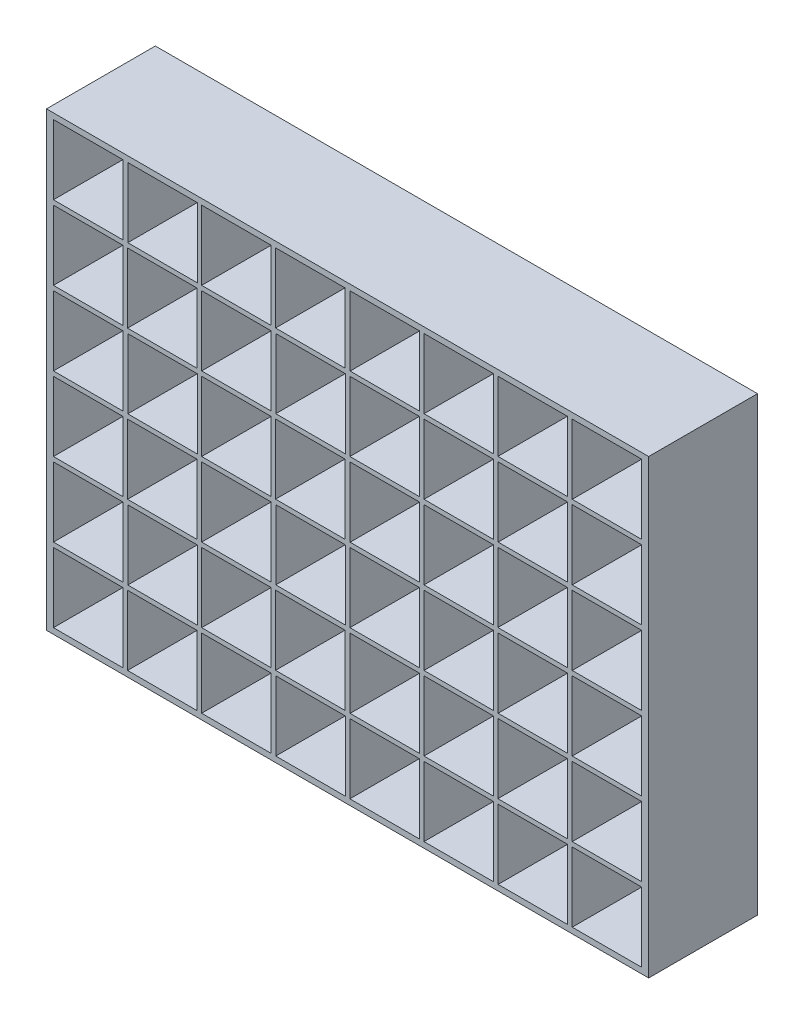
SolidWorks part; units mm, degrees
ref_plane "Front Plane" through (0, 0, 0) normal (0, 0, 1) x (1, 0, 0)
ref_plane "Top Plane" through (0, 0, 0) normal (0, 1, 0) x (1, 0, 0)
ref_plane "Right Plane" through (0, 0, 0) normal (1, 0, 0) x (0, 0, -1)
sketch "Sketch2" plane through (0, 0, 0) normal (0, 0, 1) x (1, 0, 0)
  line L0 (279.5621, 0) -> (0, 0) construction
  line L1 (0, 0) -> (-270, 0) construction
  line L2 (0, 213.5254) -> (0, 0) construction
  line L3 (0, 0) -> (0, -206.351) construction
  line L4 (279.5621, -160) -> (-260.4379, -160) construction
  line L5 (269.6997, 32) -> (-270, 32) construction
  line L6 (-270.3003, 96) -> (269.6997, 96) construction
  line L7 (254, 62) -> (194, 62)
  line L8 (269.6997, 160) -> (-270.3003, 155.1143) construction
  line L10 (-260, 195) -> (260, 195)
  line L11 (32, 207.3747) -> (32, -206.351) construction
  line L12 (-260.4379, -32) -> (279.5621, -32) construction
  line L13 (2.1959, 2) -> (62.1959, 2)
  line L14 (96, -206.351) -> (96, 207.3747) construction
  line L15 (2.1959, 2) -> (2.1959, 62)
  line L16 (160, 207.3747) -> (160, -206.351) construction
  line L17 (2.1959, 62) -> (62.1959, 62)
  line L18 (-260.4379, -96) -> (279.5621, -96) construction
  line L19 (224, -206.351) -> (224, 207.3747) construction
  line L20 (-32, 213.5254) -> (-32, -206.351) construction
  line L21 (62.1959, 2) -> (62.1959, 62)
  line L22 (-96, -206.351) -> (-96, 217.0649) construction
  line L23 (-260, 195) -> (-260, -195)
  line L24 (-160, 213.5254) -> (-160, -206.351) construction
  line L25 (-260, -195) -> (260, -195)
  line L26 (-224, -206.351) -> (-224, 207.3747) construction
  line L27 (66, 2) -> (126, 2)
  line L28 (66, 2) -> (66, 62)
  line L29 (66, 62) -> (126, 62)
  line L30 (126, 2) -> (126, 62)
  line L31 (260, 195) -> (260, -195)
  line L32 (-260, 195) -> (260, -195) construction
  line L33 (194, 2) -> (194, 62)
  line L34 (254, 2) -> (194, 2)
  line L35 (254, 2) -> (254, 62)
  line L36 (189.8041, 62) -> (129.8041, 62)
  line L37 (129.8041, 2) -> (129.8041, 62)
  line L38 (189.8041, 2) -> (129.8041, 2)
  line L39 (189.8041, 2) -> (189.8041, 62)
  line L40 (-2.1959, 62) -> (-62.1959, 62)
  line L41 (-62.1959, 2) -> (-62.1959, 62)
  line L42 (-2.1959, 2) -> (-62.1959, 2)
  line L43 (-2.1959, 2) -> (-2.1959, 62)
  line L44 (-189.8041, 2) -> (-189.8041, 62)
  line L45 (-189.8041, 2) -> (-129.8041, 2)
  line L46 (-129.8041, 2) -> (-129.8041, 62)
  line L47 (-189.8041, 62) -> (-129.8041, 62)
  line L48 (-66, 62) -> (-126, 62)
  line L49 (-126, 2) -> (-126, 62)
  line L50 (-66, 2) -> (-126, 2)
  line L51 (-66, 2) -> (-66, 62)
  line L52 (-254, 2) -> (-254, 62)
  line L53 (-254, 2) -> (-194, 2)
  line L54 (-194, 2) -> (-194, 62)
  line L55 (-254, 62) -> (-194, 62)
  line L56 (-254, 190) -> (-194, 190)
  line L57 (-194, 190) -> (-194, 130)
  line L58 (-254, 130) -> (-194, 130)
  line L59 (-254, 190) -> (-254, 130)
  line L60 (-189.8041, 190) -> (-129.8041, 190)
  line L61 (-129.8041, 190) -> (-129.8041, 130)
  line L62 (-189.8041, 130) -> (-129.8041, 130)
  line L63 (-189.8041, 190) -> (-189.8041, 130)
  line L64 (-66, 190) -> (-66, 130)
  line L65 (-66, 190) -> (-126, 190)
  line L66 (-126, 190) -> (-126, 130)
  line L67 (-66, 130) -> (-126, 130)
  line L68 (-2.1959, 190) -> (-2.1959, 130)
  line L69 (-2.1959, 190) -> (-62.1959, 190)
  line L70 (-62.1959, 190) -> (-62.1959, 130)
  line L71 (-2.1959, 130) -> (-62.1959, 130)
  line L72 (2.1959, 130) -> (62.1959, 130)
  line L73 (62.1959, 190) -> (62.1959, 130)
  line L74 (2.1959, 190) -> (62.1959, 190)
  line L75 (2.1959, 190) -> (2.1959, 130)
  line L76 (66, 130) -> (126, 130)
  line L77 (126, 190) -> (126, 130)
  line L78 (66, 190) -> (126, 190)
  line L79 (66, 190) -> (66, 130)
  line L80 (189.8041, 190) -> (189.8041, 130)
  line L81 (189.8041, 190) -> (129.8041, 190)
  line L82 (129.8041, 190) -> (129.8041, 130)
  line L83 (189.8041, 130) -> (129.8041, 130)
  line L84 (254, 190) -> (254, 130)
  line L85 (254, 190) -> (194, 190)
  line L86 (194, 190) -> (194, 130)
  line L87 (254, 130) -> (194, 130)
  line L88 (-254, -66) -> (-194, -66)
  line L89 (-194, -66) -> (-194, -126)
  line L90 (-254, -126) -> (-194, -126)
  line L91 (-254, -66) -> (-254, -126)
  line L92 (-189.8041, -66) -> (-129.8041, -66)
  line L93 (-129.8041, -66) -> (-129.8041, -126)
  line L94 (-189.8041, -126) -> (-129.8041, -126)
  line L95 (-189.8041, -66) -> (-189.8041, -126)
  line L96 (-66, -66) -> (-66, -126)
  line L97 (-66, -66) -> (-126, -66)
  line L98 (-126, -66) -> (-126, -126)
  line L99 (-66, -126) -> (-126, -126)
  line L100 (-2.1959, -66) -> (-2.1959, -126)
  line L101 (-2.1959, -66) -> (-62.1959, -66)
  line L102 (-62.1959, -66) -> (-62.1959, -126)
  line L103 (-2.1959, -126) -> (-62.1959, -126)
  line L104 (2.1959, -126) -> (62.1959, -126)
  line L105 (62.1959, -66) -> (62.1959, -126)
  line L106 (2.1959, -66) -> (62.1959, -66)
  line L107 (2.1959, -66) -> (2.1959, -126)
  line L108 (66, -126) -> (126, -126)
  line L109 (126, -66) -> (126, -126)
  line L110 (66, -66) -> (126, -66)
  line L111 (66, -66) -> (66, -126)
  line L112 (189.8041, -66) -> (189.8041, -126)
  line L113 (189.8041, -66) -> (129.8041, -66)
  line L114 (129.8041, -66) -> (129.8041, -126)
  line L115 (189.8041, -126) -> (129.8041, -126)
  line L116 (254, -66) -> (254, -126)
  line L117 (254, -66) -> (194, -66)
  line L118 (194, -66) -> (194, -126)
  line L119 (254, -126) -> (194, -126)
  line L120 (-66, 126) -> (-126, 126)
  line L121 (2, 66) -> (62, 66)
  line L122 (2, 66) -> (2, 126)
  line L123 (2, 126) -> (62, 126)
  line L124 (62, 66) -> (62, 126)
  line L125 (-260, -195) -> (260, 195) construction
  line L127 (-126, 66) -> (-126, 126)
  line L128 (-66, 66) -> (-126, 66)
  line L129 (-66, 66) -> (-66, 126)
  line L130 (190, 126) -> (130, 126)
  line L131 (130, 66) -> (130, 126)
  line L132 (190, 66) -> (130, 66)
  line L133 (190, 66) -> (190, 126)
  line L134 (254, 66) -> (194, 66)
  line L135 (66, 126) -> (126, 126)
  line L136 (66, 126) -> (66, 66)
  line L137 (66, 66) -> (126, 66)
  line L138 (126, 126) -> (126, 66)
  line L141 (194, 126) -> (194, 66)
  line L142 (254, 126) -> (194, 126)
  line L143 (254, 126) -> (254, 66)
  line L144 (-2, 66) -> (-62, 66)
  line L145 (-62, 126) -> (-62, 66)
  line L146 (-2, 126) -> (-62, 126)
  line L147 (-2, 126) -> (-2, 66)
  line L148 (-254, 126) -> (-254, 66)
  line L149 (-254, 126) -> (-194, 126)
  line L150 (-194, 126) -> (-194, 66)
  line L151 (-254, 66) -> (-194, 66)
  line L152 (-190, 126) -> (-190, 66)
  line L153 (-190, 126) -> (-130, 126)
  line L154 (-130, 126) -> (-130, 66)
  line L155 (-190, 66) -> (-130, 66)
  line L156 (-254, -62) -> (-194, -62)
  line L157 (-194, -62) -> (-194, -2)
  line L158 (-254, -2) -> (-194, -2)
  line L159 (-254, -62) -> (-254, -2)
  line L160 (-190, -62) -> (-130, -62)
  line L161 (-130, -62) -> (-130, -2)
  line L162 (-190, -2) -> (-130, -2)
  line L163 (-190, -62) -> (-190, -2)
  line L164 (-66, -2) -> (-66, -62)
  line L165 (-66, -2) -> (-126, -2)
  line L166 (-126, -2) -> (-126, -62)
  line L167 (-66, -62) -> (-126, -62)
  line L168 (-2, -62) -> (-2, -2)
  line L169 (-2, -62) -> (-62, -62)
  line L170 (-62, -62) -> (-62, -2)
  line L171 (-2, -2) -> (-62, -2)
  line L172 (2, -62) -> (62, -62)
  line L173 (62, -2) -> (62, -62)
  line L174 (2, -2) -> (62, -2)
  line L175 (2, -2) -> (2, -62)
  line L176 (66, -2) -> (126, -2)
  line L177 (126, -62) -> (126, -2)
  line L178 (66, -62) -> (126, -62)
  line L179 (66, -62) -> (66, -2)
  line L180 (190, -2) -> (190, -62)
  line L181 (190, -2) -> (130, -2)
  line L182 (130, -2) -> (130, -62)
  line L183 (190, -62) -> (130, -62)
  line L184 (254, -62) -> (254, -2)
  line L185 (254, -62) -> (194, -62)
  line L186 (194, -62) -> (194, -2)
  line L187 (254, -2) -> (194, -2)
  line L188 (-254, -130) -> (-254, -190)
  line L189 (-254, -190) -> (-194, -190)
  line L190 (-194, -130) -> (-194, -190)
  line L191 (-254, -130) -> (-194, -130)
  line L192 (-190, -130) -> (-190, -190)
  line L193 (-190, -190) -> (-130, -190)
  line L194 (-130, -130) -> (-130, -190)
  line L195 (-190, -130) -> (-130, -130)
  line L196 (-66, -190) -> (-126, -190)
  line L197 (-126, -190) -> (-126, -130)
  line L198 (-66, -130) -> (-126, -130)
  line L199 (-66, -190) -> (-66, -130)
  line L200 (-2, -130) -> (-62, -130)
  line L201 (-62, -130) -> (-62, -190)
  line L202 (-2, -190) -> (-62, -190)
  line L203 (-2, -130) -> (-2, -190)
  line L204 (66, -130) -> (66, -190)
  line L205 (66, -130) -> (126, -130)
  line L206 (126, -130) -> (126, -190)
  line L207 (66, -190) -> (126, -190)
  line L208 (190, -190) -> (130, -190)
  line L209 (130, -190) -> (130, -130)
  line L210 (190, -130) -> (130, -130)
  line L211 (190, -190) -> (190, -130)
  line L212 (254, -130) -> (194, -130)
  line L213 (194, -130) -> (194, -190)
  line L214 (254, -190) -> (194, -190)
  line L215 (254, -130) -> (254, -190)
  line L216 (2, -190) -> (2, -130)
  line L217 (2, -190) -> (62, -190)
  line L218 (62, -190) -> (62, -130)
  line L219 (2, -130) -> (62, -130)
  point P38 (32, 32)
  point P43 (96, 32)
  point P136 (32, 96)
  point P149 (96, 96)
  dimension "D1" = 32
  dimension "D2" = 64
  dimension "D3" = 64
  dimension "D4" = 64
  dimension "D5" = 64
  dimension "D6" = 64
  dimension "D7" = 64
  dimension "D8" = 32
  dimension "D9" = 64
  dimension "D10" = 520
  dimension "D11" = 64
  dimension "D12" = 32
  dimension "D13" = 390
  dimension "D14" = 64
  dimension "D15" = 64
  dimension "D18" = 32
extrude "Boss-Extrude1" add sketch "Sketch2" along normal blind 90
sketch "Sketch5" plane through (0, 0, 0) normal (0, 0, -1) x (-1, 0, 0)
  line L1 (-260, 195) -> (260, 195)
  line L2 (-260, 195) -> (-260, -195)
  line L3 (-260, -195) -> (260, -195)
  line L4 (260, 195) -> (260, -195)
  line L5 (-260, 195) -> (260, -195) construction
  line L6 (-260, -195) -> (260, 195) construction
  point P0 (0, 0)
extrude "Boss-Extrude3" add sketch "Sketch5" along normal blind 4 contours L2 L1 L4 L3
